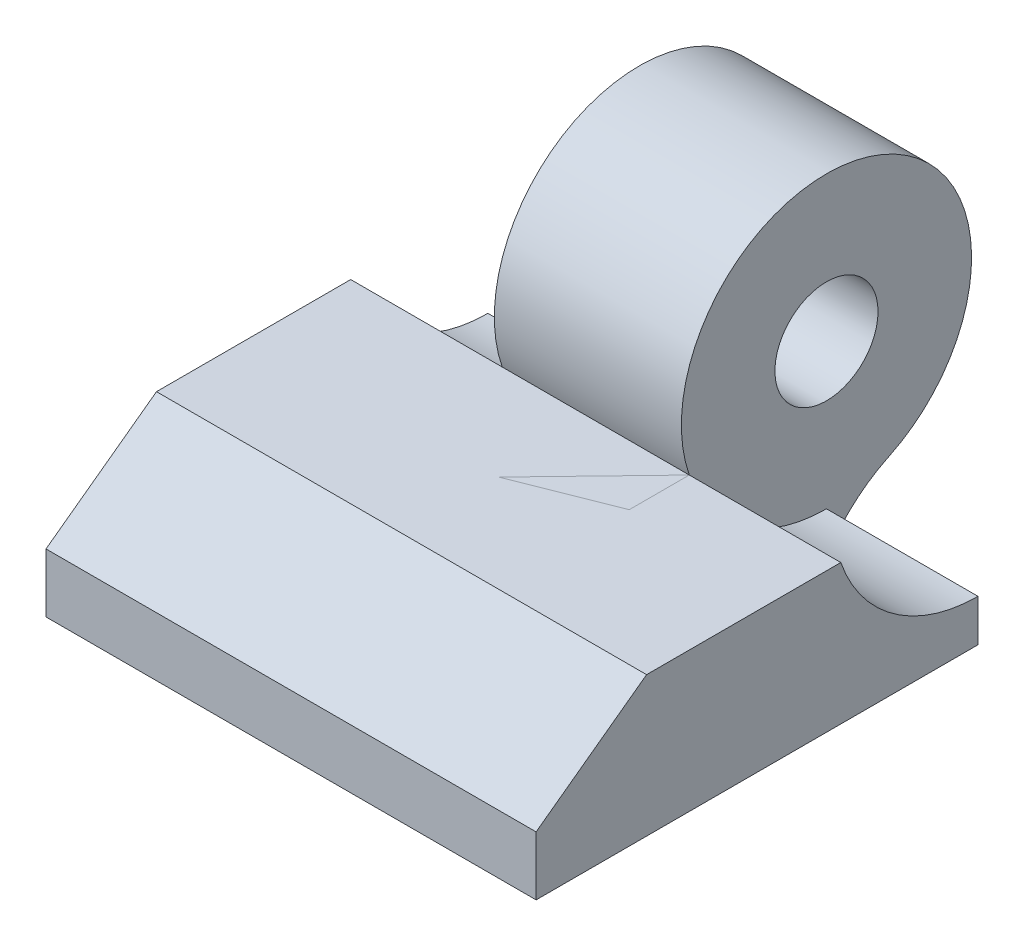
SolidWorks part; units mm, degrees
ref_plane "Front Plane" through (0, 0, 0) normal (0, 0, 1) x (1, 0, 0)
ref_plane "Top Plane" through (0, 0, 0) normal (0, 1, 0) x (1, 0, 0)
ref_plane "Right Plane" through (0, 0, 0) normal (1, 0, 0) x (0, 0, -1)
sketch "Sketch1" plane through (0, 0, 0) normal (1, 0, 0) x (0, 0, -1)
  line L0 (0, -12.7) -> (-30, -12.7)
  line L1 (-30, -12.7) -> (-30, -8.7)
  line L2 (-30, -8.7) -> (-22.5, -3.2049)
  line L3 (-22.5, -3.2049) -> (-9.314, -3.2049)
  line L5 (0, -12.7) -> (0, -9.85)
  arc A0 (0, -9.525) -> (-8.9696, -3.2049) centre (0, 0) ccw construction
  arc A1 (0, -11) -> (-10.5228, -3.2049) centre (0, 0) ccw construction
  circle A2 centre (0, 0) radius 3.5
  arc A3 (0, -9.85) -> (-9.314, -3.2049) centre (0, 0) ccw
  dimension "D1" = 19.05
  dimension "D2" = 6.35
  dimension "D6" = 22
  dimension "D9" = 7
  dimension "D3" = 9.4951
  dimension "D4" = 4
  dimension "D5" = 12.7
  dimension "D7" = 7.5
  dimension "D8" = 30
extrude "Boss-Extrude1" add sketch "Sketch1" along normal mid plane 12.7
sketch "Sketch4" plane through (0, 0, 0) normal (1, 0, 0) x (0, 0, -1)
  line L5 (0, -12.7) -> (0, -9.85)
  line L6 (-9.314, -3.2049) -> (-22.5, -3.2049)
  line L7 (-22.5, -3.2049) -> (-30, -8.7)
  line L8 (-30, -8.7) -> (-30, -12.7)
  line L9 (-30, -12.7) -> (0, -12.7)
  line L10 (0, -12.7) -> (0, -9.85)
  line L11 (-9.314, -3.2049) -> (-22.5, -3.2049)
  line L12 (-22.5, -3.2049) -> (-30, -8.7)
  line L13 (-30, -8.7) -> (-30, -12.7)
  line L14 (-30, -12.7) -> (0, -12.7)
  circle A0 centre (0, 0) radius 9.85
  arc A1 (0, -9.85) -> (-9.314, -3.2049) centre (0, 0) ccw
  arc A2 (0, -9.85) -> (-9.314, -3.2049) centre (0, 0) ccw
  dimension "D1" = 0
extrude "Boss-Extrude2" add sketch "Sketch4" along normal mid plane 33.274 separate body contours A0 L11 L12 L13 L14 L10
fillet "Fillet1" radius 10 1 edges at (0, -9.85, 0)
